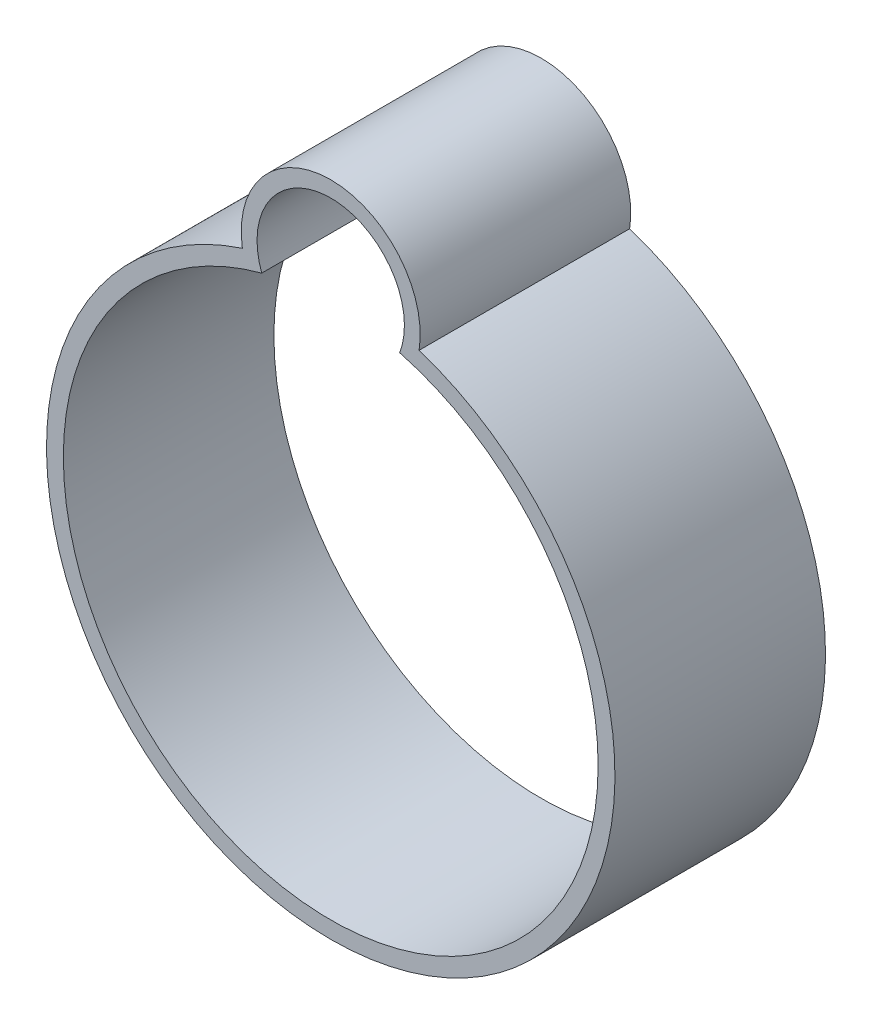
SolidWorks part; units mm, degrees
ref_plane "正面" through (0, 0, 0) normal (0, 0, 1) x (1, 0, 0)
ref_plane "平面" through (0, 0, 0) normal (0, 1, 0) x (1, 0, 0)
ref_plane "右側面" through (0, 0, 0) normal (1, 0, 0) x (0, 0, -1)
sketch "ｽｹｯﾁ1" plane through (0, 0, 0) normal (0, 0, 1) x (1, 0, 0)
  arc A2 (3.2768, 12.27) -> (-3.2768, 12.27) centre (0, 13.5) ccw
  arc A3 (-3.2768, 12.27) -> (3.2768, 12.27) centre (0, 0) ccw
  arc A4 (-4.197, 12.831) -> (4.197, 12.831) centre (0, 0) ccw
  arc A5 (4.197, 12.831) -> (-4.197, 12.831) centre (0, 13.5) ccw
  dimension "D1" = 25.4
  dimension "D2" = 27
  dimension "D3" = 7
  dimension "D4" = 13.5
  dimension "D5" = 8.5
extrude "ﾎﾞｽ - 押し出し1" add sketch "ｽｹｯﾁ1" along normal blind 10
sketch "ｽｹｯﾁ2" plane through (0, 0, 0) normal (1, 0, 0) x (0, 0, -1)
  line L0 (0, 15.2905) -> (-10, 15.2905)
  line L1 (0, 12.831) -> (0, 17.75) construction
  line L2 (-10, 17.75) -> (-10, 12.831) construction
ref_axis "軸1" through (0, 15.2905, 0.2279) along (0, 0, 1)
